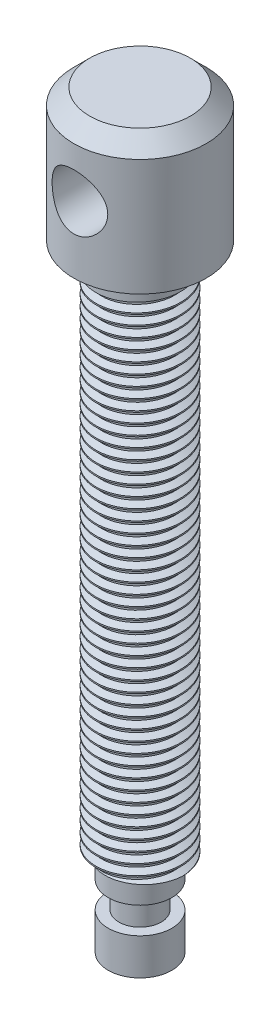
SolidWorks part; units mm, degrees
material "Chrome Stainless Steel"
ref_plane "Front Plane" through (0, 0, 0) normal (0, 0, 1) x (1, 0, 0)
ref_plane "Top Plane" through (0, 0, 0) normal (0, 1, 0) x (1, 0, 0)
ref_plane "Right Plane" through (0, 0, 0) normal (1, 0, 0) x (0, 0, -1)
sketch "Sketch1" plane through (0, 0, 0) normal (0, 0, 1) x (1, 0, 0)
  line L0 (0, 0) -> (145319.0532, 0) construction
  line L1 (0, 0) -> (0, -145319.0532) construction
  line L2 (0, 0) -> (0, 143)
  line L3 (0, 143) -> (12.5, 143)
  line L4 (12.5, 143) -> (12.5, 118)
  line L5 (12.5, 118) -> (8, 118)
  line L6 (8, 118) -> (8, 18)
  line L7 (8, 18) -> (6, 18)
  line L8 (6, 18) -> (6, 13.5)
  line L9 (6, 13.5) -> (4, 13.5)
  line L10 (4, 13.5) -> (4, 8.5)
  line L11 (4, 8.5) -> (6, 8.5)
  line L12 (6, 8.5) -> (6, 1.6077)
  arc A0 (6, 1.6077) -> (0, 0) centre (0, 12) cw
  dimension "D10" = 12
  dimension "D1" = 143
  dimension "D2" = 25
  dimension "D3" = 25
  dimension "D4" = 16
  dimension "D5" = 18
  dimension "D6" = 12
  dimension "D7" = 4.5
  dimension "D8" = 5
  dimension "D9" = 8
revolve "Revolve1" add sketch "Sketch1" angle 360 about L2
chamfer "Chamfer1" distance 3 angle 45 1 edges at (0, 143, -12.5)
sketch "Sketch2" plane through (0, 0, 0) normal (0, 0, 1) x (1, 0, 0)
  line L0 (9.5, 143) -> (-9.5, 143) construction
  circle A0 centre (0, 130.5) radius 5.25
  dimension "D1" = 10.5
  dimension "D2" = 12.5
extrude "Cut-Extrude1" cut sketch "Sketch2" against normal mid plane 40
thread "Thread1" pitch 2 method cut profile "Thread Profile1" start angle 0, offset 2, length 97, pitch 2, diameter 16
ref_plane "Plane1" through (8, 16, 0) normal (0, 0, 1) x (1, 0, 0)
sketch "Thread Profile1" plane through (8, 16, 0) normal (0, 0, 1) x (1, 0, 0)
  line L0 (0, 0) -> (0, 2) construction
  line L11 (0, 0) -> (0, 1.75)
  line L12 (0, 1.75) -> (-1.0825, 1.125)
  line L13 (-1.0825, 1.125) -> (-1.0825, 0.625)
  line L15 (-1.0825, 0.625) -> (0, 0)
  line L17 (-1.0825, 0.875) -> (0, 0.875) construction
  point P2 (0, 0)
  dimension "Pitch" = 2
  dimension "Profile_Angle" = 60
  dimension "Profile_Land" = 0.5
  dimension "Profile_Height" = 1.0825
